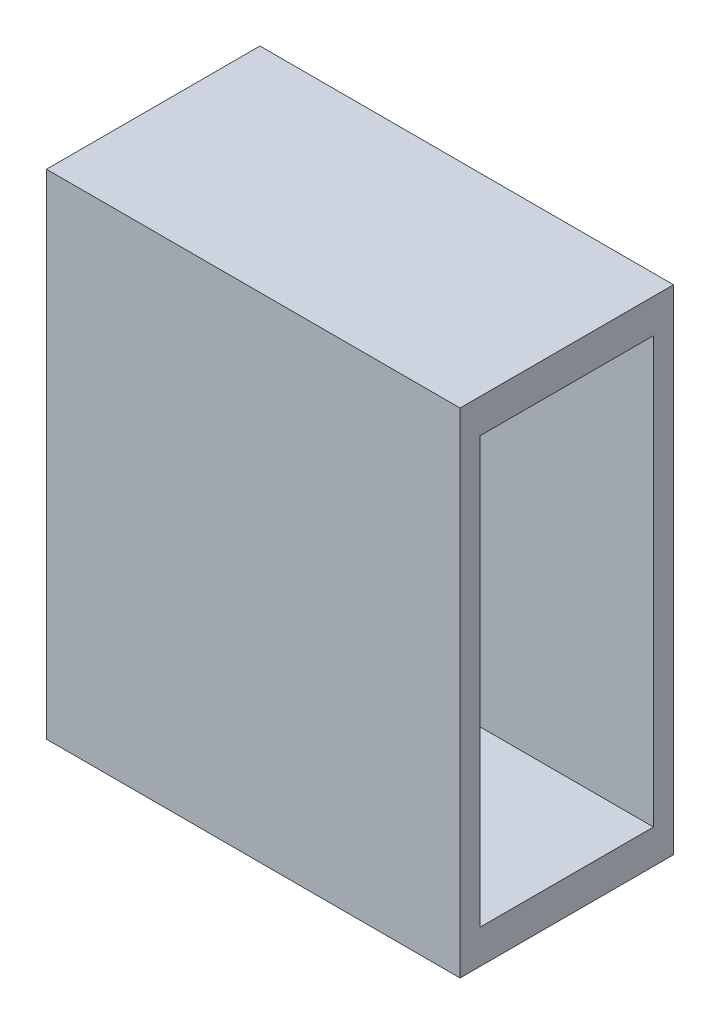
SolidWorks part; units mm, degrees
ref_plane "Front Plane" through (0, 0, 0) normal (1, 0, 0) x (0, 1, 0)
ref_plane "Top Plane" through (0, 0, 0) normal (0, 0, 1) x (0, 1, 0)
ref_plane "Right Plane" through (0, 0, 0) normal (0, 1, 0) x (-1, 0, 0)
sketch "Sketch1" plane through (0, 0, 0) normal (1, 0, 0) x (0, 1, 0)
  line L5 (-37, 8) -> (-30.25, 8) construction
  line L6 (-37, 16) -> (0, 16)
  line L11 (-37, 16) -> (-37, 0)
  line L12 (-37, 0) -> (0, 0)
  line L20 (0, 16) -> (0, 0)
  line L21 (-30.25, 14.5) -> (-6.75, 14.5)
  line L22 (-30.25, 14.5) -> (-30.25, 1.5)
  line L23 (-30.25, 1.5) -> (-6.75, 1.5)
  line L24 (-6.75, 14.5) -> (-6.75, 1.5)
  line L25 (-6.75, 8) -> (0, 8) construction
  line L26 (-18.5, 0) -> (-18.5, 1.5) construction
  line L27 (-18.5, 16) -> (-18.5, 14.5) construction
  line L29 (-34.45, 1.5) -> (-2.55, 1.5)
  line L30 (-34.45, 1.5) -> (-34.45, 14.5)
  line L31 (-34.45, 14.5) -> (-2.55, 14.5)
  line L32 (-2.55, 1.5) -> (-2.55, 14.5)
  dimension "D1" = 4.2
  dimension "D2" = 13
  dimension "D3" = 4.2
  dimension "D6" = 37
  dimension "D7" = 23.5
  dimension "D9" = 1.5
extrude "Boss-Extrude1" add sketch "Sketch1" along normal blind 26 contours L20 L6 L11 L12 L21 L24 L23 L22 region at (0, -18.5, 15.5969)
extrude "Boss-Extrude2" add sketch "Sketch1<3>" along normal blind 2 contours L31 L30 L29 L22 | L29 L32 L31 L24 region at (0, -32.35, 8) region at (0, -4.65, 8)
sketch "Sketch1<3>" plane through (0, 0, 0) normal (1, 0, 0) x (0, 1, 0) same geometry as "Sketch1"
sketch "Sketch2" plane through (26, 0, 0) normal (1, 0, 0) x (0, 1, 0)
  line L1 (-37, 16) -> (0, 16)
  line L2 (-37, 16) -> (-37, 0)
  line L3 (-37, 0) -> (0, 0)
  line L4 (0, 16) -> (0, 0)
sketch "Sketch3" plane through (0, 0, 0) normal (-1, 0, 0) x (0, -1, 0)
  line L1 (0, 16) -> (37, 16)
  line L2 (0, 16) -> (0, 0)
  line L3 (0, 0) -> (37, 0)
  line L4 (37, 16) -> (37, 0)
  line L5 (2.55, 14.5) -> (34.45, 14.5)
  line L6 (2.55, 14.5) -> (2.55, 1.5)
  line L7 (2.55, 1.5) -> (34.45, 1.5)
  line L8 (34.45, 14.5) -> (34.45, 1.5)
extrude "Boss-Extrude4" add sketch "Sketch3" along normal blind 3.5
sketch "Sketch5" plane through (-3.5, 0, 0) normal (-1, 0, 0) x (0, -1, 0)
  line L0 (37, 8) -> (30.25, 8) construction
  line L1 (0, 16) -> (37, 16)
  line L2 (0, 16) -> (0, 0)
  line L3 (0, 0) -> (37, 0)
  line L4 (37, 16) -> (37, 0)
  line L5 (30.25, 14.5) -> (30.25, 1.5) construction
  circle A0 centre (23.25, 8) radius 5.2
  dimension "D1" = 10.4
  dimension "D2" = 7
extrude "Boss-Extrude5" add sketch "Sketch5" along normal blind 1.5
ref_plane "Plane1" through (26, 0, 16) normal (0, 0, -1) x (-1, 0, 0)
sketch "Sketch9" plane through (0, 0, 0) normal (0, 1, 0) x (-1, 0, 0)
  line L0 (-26, 8) -> (5, 8) construction
  line L3 (-26, 16) -> (-26, 0) construction
  line L4 (5, 16) -> (5, 0) construction
  line L5 (-2, 5.65) -> (-17, 4.4)
  line L6 (-2, 10.35) -> (-17, 11.6)
  circle A2 centre (-17, 8) radius 3.6
  circle A3 centre (-2, 8) radius 2.35
  circle A4 centre (-17, 8) radius 0.15
  circle A5 centre (-2, 8) radius 0.15
  dimension "D1" = 0.3
  dimension "D4" = 7.2
  dimension "D5" = 4.7
  dimension "D6" = 15
  dimension "D7" = 9
sketch "Sketch10" plane through (0, 0, 16) normal (0, 0, 1) x (1, 0, 0)
sketch "Sketch11" plane through (0, -37, 0) normal (0, -1, 0) x (1, 0, 0)
  line L0 (2.375, 8) -> (17.375, 8) construction
  line L1 (17.375, 4.4) -> (2.375, 5.65)
  line L2 (17.375, 11.6) -> (2.375, 10.35)
  line L3 (-5, 8) -> (0.025, 8) construction
  line L4 (-5, 0) -> (-5, 16) construction
  line L5 (20.975, 8) -> (26, 8) construction
  line L6 (26, 16) -> (26, 0) construction
  line L7 (2.375, 10.35) -> (2.375, 16) construction
  line L8 (26, 16) -> (-5, 16) construction
  line L9 (2.375, 0) -> (2.375, 5.65) construction
  line L10 (26, 0) -> (-5, 0) construction
  circle A0 centre (2.375, 8) radius 2.35
  circle A1 centre (17.375, 8) radius 3.6
  circle A2 centre (2.375, 8) radius 0.15
  circle A3 centre (17.375, 8) radius 0.15
  dimension "D1" = 4.7
  dimension "D2" = 7.2
  dimension "D4" = 0.3
  dimension "D3" = 15
extrude "Cut-Extrude5" cut sketch "Sketch11" against normal blind 1.5 contours A1 L2 A0 L1 | A1 A3 | L1 A0 L2 A2 | A3 | A2 region at (17.0855, -37, 4.5263) region at (9.5724, -37, 8) region at (0.0915, -37, 8) region at (2.375, -37, 8) region at (17.375, -37, 8)
extrude "Cut-Extrude12" cut sketch "Sketch11<7>" against normal blind 2 contours A2 | A3 region at (2.375, -37, 8) region at (17.375, -37, 8)
sketch "Sketch11<7>" plane through (0, -37, 0) normal (0, -1, 0) x (1, 0, 0) same geometry as "Sketch11"
